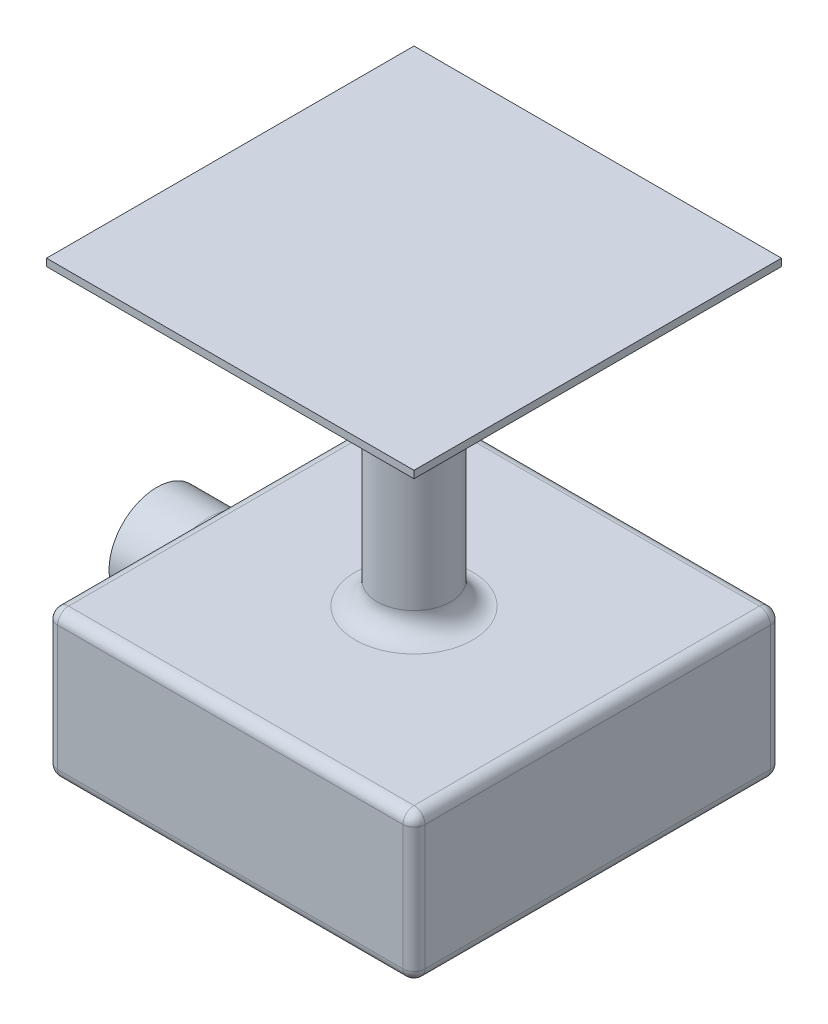
SolidWorks part; units mm, degrees
ref_plane "Front Plane" through (0, 0, 0) normal (0, 0, 1) x (1, 0, 0)
ref_plane "Top Plane" through (0, 0, 0) normal (0, 1, 0) x (1, 0, 0)
ref_plane "Right Plane" through (0, 0, 0) normal (1, 0, 0) x (0, 0, -1)
sketch "Sketch1" plane through (0, 0, 0) normal (0, 1, 0) x (1, 0, 0)
  line L1 (250, -250) -> (-250, -250)
  line L2 (250, -250) -> (250, 250)
  line L3 (250, 250) -> (-250, 250)
  line L4 (-250, -250) -> (-250, 250)
  line L5 (250, -250) -> (-250, 250) construction
  line L6 (250, 250) -> (-250, -250) construction
  point P0 (0, 0)
  dimension "D1" = 500
  dimension "D2" = 500
extrude "Boss-Extrude1" add sketch "Sketch1" along normal blind 200
sketch "Sketch2" plane through (-250, 0, 0) normal (-1, 0, 0) x (0, 0, 1)
  line L0 (0, 200) -> (0, 0) construction
  line L1 (-250, 200) -> (250, 200) construction
  circle A0 centre (0, 100) radius 65
extrude "Boss-Extrude2" add sketch "Sketch2" along normal blind 100
fillet "Fillet1" radius 15 12 edges at (0, 200, -250) (0, 200, 250) (-250, 100, -250) (-250, 200, 0) (-250, 100, 250) (250, 100, 250) (250, 200, 0) (250, 100, -250) (0, 0, 250) (250, 0, 0) (0, 0, -250) (-250, 0, 0)
sketch "Sketch3" plane through (-350, 0, 0) normal (-1, 0, 0) x (0, 0, 1)
  circle A0 centre (0, 100) radius 45
extrude "Cut-Extrude1" cut sketch "Sketch3" against normal blind 20
fillet "Fillet2" radius 10 2 edges at (-350, 100, 45) (-330, 100, 45)
sketch "Sketch4" plane through (0, 0, 0) normal (1, 0, 0) x (0, 0, -1)
  line L0 (0, -131.2561) -> (0, 852.985) construction
  line L1 (0, 200) -> (-50, 200)
  line L3 (0, 600) -> (-50, 600)
  line L4 (-50, 200) -> (-50, 600)
  line L5 (-11.4724, 384.6047) -> (-50, 600) construction
  line L6 (-11.4724, 384.6047) -> (-50, 200) construction
  line L7 (0, 600) -> (0, 200)
  line L8 (-235, 200) -> (235, 200) construction
  point P4 (-11.4724, 384.6047)
  point P11 (0, 200)
  dimension "D1" = 50
  dimension "D2" = 400
revolve "Revolve1" add sketch "Sketch4" angle 360 about L7
sketch "Sketch5" plane through (0, 600, 0) normal (0, 1, 0) x (1, 0, 0)
  line L1 (250, -250) -> (-250, -250)
  line L2 (250, -250) -> (250, 250)
  line L3 (250, 250) -> (-250, 250)
  line L4 (-250, -250) -> (-250, 250)
  line L5 (250, -250) -> (-250, 250) construction
  line L6 (250, 250) -> (-250, -250) construction
  point P0 (0, 0)
  dimension "D1" = 500
  dimension "D2" = 500
extrude "Boss-Extrude3" add sketch "Sketch5" along normal blind 10
fillet "Fillet3" radius 30 1 edges at (-250, 100, 65)
fillet "Fillet4" radius 30 2 edges at (0, 600, 50) (0, 200, 50)
